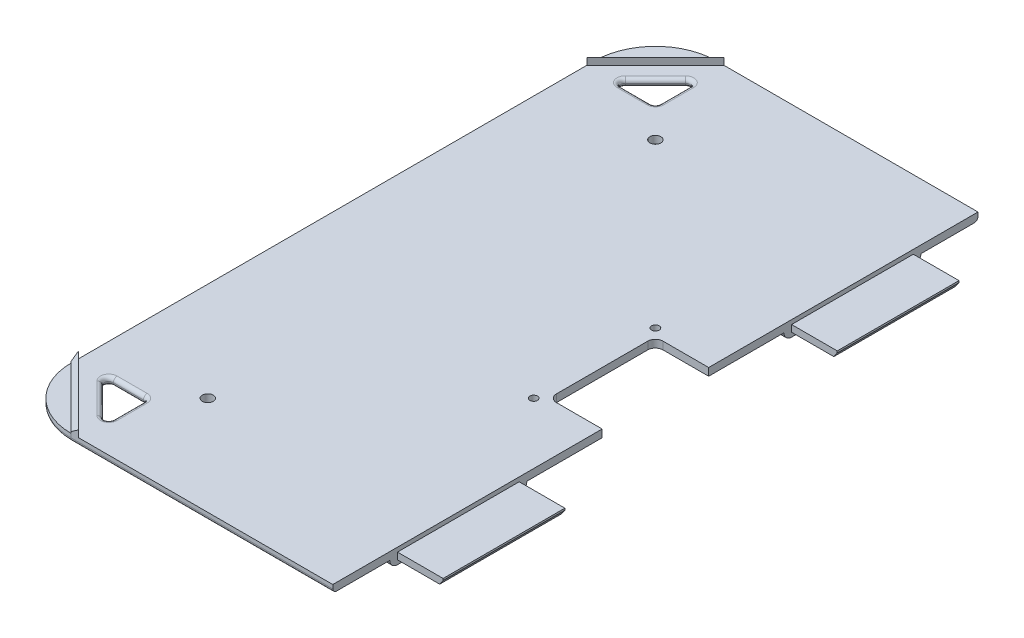
SolidWorks part; units mm, degrees
ref_plane "Front Plane" through (0, 0, 0) normal (0, 0, 1) x (1, 0, 0)
ref_plane "Top Plane" through (0, 0, 0) normal (0, 1, 0) x (1, 0, 0)
ref_plane "Right Plane" through (0, 0, 0) normal (1, 0, 0) x (0, 0, -1)
sketch "Sketch1" plane through (0, 0, 0) normal (0, 1, 0) x (1, 0, 0)
  line L0 (0, -134.62) -> (0, 134.62)
  line L1 (-134.62, -134.62) -> (134.62, -134.62)
  line L2 (-134.62, -134.62) -> (-134.62, 134.62)
  line L3 (-134.62, 134.62) -> (134.62, 134.62)
  line L4 (134.62, -134.62) -> (134.62, 134.62)
  line L5 (-134.62, -134.62) -> (134.62, 134.62) construction
  line L6 (-134.62, 134.62) -> (134.62, -134.62) construction
  point P0 (0, 0)
  point P9 (0, 0)
  dimension "D1" = 269.24
extrude "Boss-Extrude1" add sketch "Sketch1" along normal blind 3.175 contours L3 L2 L1 L0 region at (-67.31, 0, 0)
sketch "Sketch2" plane through (0, 3.175, 0) normal (0, 1, 0) x (1, 0, 0)
  line L0 (-109.22, -134.62) -> (-134.62, -109.22)
  line L1 (-109.22, -134.62) -> (-106.045, -134.62)
  line L2 (-106.045, -134.62) -> (-134.62, -106.045)
  line L3 (-134.62, -106.045) -> (-134.62, -109.22)
  line L4 (0, 134.62) -> (-134.62, 134.62)
  line L5 (-134.62, 134.62) -> (-134.62, -134.62)
  line L6 (-134.62, -134.62) -> (0, -134.62)
  line L7 (0, -134.62) -> (0, 134.62)
  line L8 (0, 134.62) -> (-134.62, 134.62)
  line L9 (-134.62, 134.62) -> (-134.62, -134.62)
  line L10 (-134.62, -134.62) -> (0, -134.62)
  line L11 (0, -134.62) -> (0, 134.62)
  line L12 (-109.22, 134.62) -> (-134.62, 109.22)
  line L13 (-134.62, 109.22) -> (-134.62, 106.045)
  line L14 (-134.62, 106.045) -> (-106.045, 134.62)
  line L15 (-106.045, 134.62) -> (-109.22, 134.62)
  line L16 (-120.3325, 120.3325) -> (-115.3934, 115.3934)
  line L17 (-120.3325, -120.3325) -> (-115.3934, -115.3934)
  line L18 (-124.9184, -105.8684) -> (-105.8684, -124.9184)
  line L19 (-105.8684, -124.9184) -> (-105.8684, -105.8684)
  line L20 (-105.8684, -105.8684) -> (-124.9184, -105.8684)
  line L21 (-124.9184, 105.8684) -> (-105.8684, 124.9184)
  line L22 (-105.8684, 124.9184) -> (-105.8684, 105.8684)
  line L23 (-105.8684, 105.8684) -> (-124.9184, 105.8684)
  line L24 (-120.3325, 120.3325) -> (-93.3917, 93.3917)
  line L25 (-120.3325, -120.3325) -> (-93.3917, -93.3917)
  circle A0 centre (-93.3917, 93.3917) radius 2.286
  circle A1 centre (-93.3917, -93.3917) radius 2.286
  point P12 (-120.3325, -120.3325)
  point P14 (-120.3325, 120.3325)
  point P21 (-115.3934, -115.3934)
  point P25 (-115.3934, 115.3934)
  line M24 (-134.62, 134.62) -> (-134.62, -134.62)
  line M25 (-134.62, -134.62) -> (0, -134.62)
  dimension "D17" = 4.572
  dimension "D2" = 25.4
  dimension "D3" = 25.4
  dimension "D4" = 3.175
  dimension "D5" = 25.4
  dimension "D6" = 3.175
  dimension "D7" = 25.4
  dimension "D8" = 3.175
  dimension "D9" = 6.985
  dimension "D10" = 6.985
  dimension "D11" = 90
  dimension "D12" = 90
  dimension "D13" = 19.05
  dimension "D14" = 90
  dimension "D15" = 19.05
  dimension "D16" = 38.1
  dimension "D18" = 90
  dimension "D19" = 90
  dimension "D1" = 0
extrude "Boss-Extrude2" add sketch "Sketch2" along normal blind 3.175 contours L9 L14 L8 L12 | L2 L0 M25 M24 region at (-121.1107, 3.175, 121.1107) region at (-121.1107, 3.175, -121.1107)
extrude "Cut-Extrude1" cut sketch "Sketch2<3>" against normal up to next contours L23 L21 L22 | L19 L20 L18 | A1 | A0
sketch "Sketch2<3>" plane through (0, 3.175, 0) normal (0, 1, 0) x (1, 0, 0) same geometry as "Sketch2"
chamfer "Chamfer1" distance 2.54 2 edges at (-121.92, 6.35, -121.92) (-121.92, 6.35, 121.92)
fillet "Fillet1" radius 1.905 6 edges at (-105.8684, 1.5875, -105.8684) (-124.9184, 1.5875, -105.8684) (-105.8684, 1.5875, -124.9184) (-105.8684, 1.5875, 124.9184) (-105.8684, 1.5875, 105.8684) (-124.9184, 1.5875, 105.8684)
fillet "Fillet2" radius 1.5875 24 edges at (-107.0443, 0, 122.0793) (-105.8684, 0, 114.0463) (-106.4263, 0, 106.4263) (-114.0463, 0, 105.8684) (-122.0793, 0, 107.0443) (-122.0793, 3.175, 107.0443) (-114.0463, 3.175, 105.8684) (-106.4263, 3.175, 106.4263) (-105.8684, 3.175, 114.0463) (-107.0443, 3.175, 122.0793) (-122.0793, 3.175, -107.0443) (-114.0463, 3.175, -105.8684) (-106.4263, 3.175, -106.4263) (-105.8684, 3.175, -114.0463) (-107.0443, 3.175, -122.0793) (-107.0443, 0, -122.0793) (-105.8684, 0, -114.0463) (-106.4263, 0, -106.4263) (-114.0463, 0, -105.8684) (-122.0793, 0, -107.0443) (-115.3934, 0, 115.3934) (-115.3934, 3.175, 115.3934) (-115.3934, 3.175, -115.3934) (-115.3934, 0, -115.3934)
fillet "Fillet3" radius 25.4 2 edges at (-134.62, 1.5875, 134.62) (-134.62, 1.5875, -134.62)
fillet "Fillet4" radius 1.5875 5 edges at (-127.1805, 0, -127.1805) (-54.61, 0, -134.62) (-134.62, 0, 0) (-127.1805, 0, 127.1805) (-54.61, 0, 134.62)
sketch "Sketch3" plane through (0, 0, 0) normal (0, -1, 0) x (1, 0, 0)
  line L1 (0, 28.575) -> (-31.75, 28.575)
  line L2 (0, 28.575) -> (0, -28.575)
  line L3 (0, -28.575) -> (-31.75, -28.575)
  line L4 (-109.22, -133.0325) -> (0, -133.0325)
  line L5 (0, -133.0325) -> (0, 133.0325)
  line L6 (0, 133.0325) -> (-109.22, 133.0325)
  line L7 (-133.0325, 109.22) -> (-133.0325, -109.22)
  line L8 (-109.22, -133.0325) -> (0, -133.0325)
  line L9 (0, -133.0325) -> (0, 133.0325)
  line L10 (0, 133.0325) -> (-109.22, 133.0325)
  line L11 (-133.0325, 109.22) -> (-133.0325, -109.22)
  line L12 (-31.75, 28.575) -> (-31.75, -28.575)
  line L13 (-31.75, 110.8075) -> (0, 110.8075)
  line L14 (-31.75, 110.8075) -> (-31.75, 53.6575)
  line L15 (-31.75, 53.6575) -> (0, 53.6575)
  line L16 (0, 110.8075) -> (0, 53.6575)
  line L17 (-31.75, -53.6575) -> (0, -53.6575)
  line L18 (-31.75, -53.6575) -> (-31.75, -110.8075)
  line L19 (-31.75, -110.8075) -> (0, -110.8075)
  line L20 (0, -53.6575) -> (0, -110.8075)
  arc A2 (-133.0325, -109.22) -> (-109.22, -133.0325) centre (-109.22, -109.22) ccw
  arc A3 (-109.22, 133.0325) -> (-133.0325, 109.22) centre (-109.22, 109.22) ccw
  arc A4 (-133.0325, -109.22) -> (-109.22, -133.0325) centre (-109.22, -109.22) ccw
  arc A5 (-109.22, 133.0325) -> (-133.0325, 109.22) centre (-109.22, 109.22) ccw
  point P12 (0, 0)
  point P22 (-31.75, -82.2325)
  point P23 (-31.75, 82.2325)
  dimension "D2" = 57.15
  dimension "D3" = 31.75
  dimension "D4" = 50.8
  dimension "D5" = 50.8
  dimension "D1" = 0
extrude "Boss-Extrude3" add sketch "Sketch3" along normal blind 3.175 contours L14 L15 L9 L13 | L18 L19 L9 L17 region at (-15.875, 0, 82.2325) region at (-15.875, 0, -82.2325)
sketch "Sketch4" plane through (0, 0, 0) normal (1, 0, 0) x (0, 0, -1)
  line L0 (-110.8075, 0) -> (-110.8075, 3.175)
  line L1 (-53.6575, 0) -> (-53.6575, 3.175)
  line L2 (53.6575, 0) -> (53.6575, 3.175)
  line L3 (28.575, 0) -> (28.575, 3.175)
  line L4 (53.6575, 0) -> (53.6575, 3.175)
  line L5 (110.8075, 0) -> (110.8075, 3.175)
  line L6 (28.575, 3.175) -> (53.6575, 3.175)
  line L7 (-53.6575, 3.175) -> (-110.8075, 3.175)
  line L9 (107.6325, -1.397) -> (56.8325, -1.397)
  line L10 (107.6325, -1.397) -> (107.6325, 1.397)
  line L11 (107.6325, 1.397) -> (56.8325, 1.397)
  line L12 (56.8325, -1.397) -> (56.8325, 1.397)
  line L13 (107.6325, -1.397) -> (56.8325, 1.397) construction
  line L14 (107.6325, 1.397) -> (56.8325, -1.397) construction
  line L15 (25.4, -1.397) -> (-25.4, -1.397)
  line L16 (-133.0325, 0) -> (-110.8075, 0)
  line L17 (-110.8075, 0) -> (-110.8075, -3.175)
  line L18 (-110.8075, -3.175) -> (-53.6575, -3.175)
  line L19 (-53.6575, -3.175) -> (-53.6575, 0)
  line L20 (-53.6575, 0) -> (53.6575, 0)
  line L25 (53.6575, 0) -> (53.6575, -3.175)
  line L26 (53.6575, -3.175) -> (110.8075, -3.175)
  line L27 (110.8075, -3.175) -> (110.8075, 0)
  line L28 (110.8075, 0) -> (133.0325, 0)
  line L29 (134.62, 1.5875) -> (134.62, 3.175)
  line L30 (134.62, 3.175) -> (-134.62, 3.175)
  line L31 (-134.62, 3.175) -> (-134.62, 1.5875)
  line L33 (-110.8075, 0) -> (-110.8075, -3.175)
  line L34 (-110.8075, -3.175) -> (-53.6575, -3.175)
  line L35 (-53.6575, -3.175) -> (-53.6575, 0)
  line L41 (53.6575, 0) -> (53.6575, -3.175)
  line L42 (53.6575, -3.175) -> (110.8075, -3.175)
  line L43 (110.8075, -3.175) -> (110.8075, 0)
  line L46 (110.8075, 3.175) -> (53.6575, 3.175)
  line L48 (25.4, -1.397) -> (25.4, 1.397)
  line L49 (25.4, 1.397) -> (-25.4, 1.397)
  line L50 (-25.4, -1.397) -> (-25.4, 1.397)
  line L51 (25.4, -1.397) -> (-25.4, 1.397) construction
  line L52 (25.4, 1.397) -> (-25.4, -1.397) construction
  line L53 (-56.8325, -1.397) -> (-107.6325, -1.397)
  line L54 (-56.8325, -1.397) -> (-56.8325, 1.397)
  line L55 (-56.8325, 1.397) -> (-107.6325, 1.397)
  line L56 (-107.6325, -1.397) -> (-107.6325, 1.397)
  line L57 (-56.8325, -1.397) -> (-107.6325, 1.397) construction
  line L58 (-56.8325, 1.397) -> (-107.6325, -1.397) construction
  arc A2 (133.0325, 0) -> (134.62, 1.5875) centre (133.0325, 1.5875) ccw
  arc A3 (-134.62, 1.5875) -> (-133.0325, 0) centre (-133.0325, 1.5875) ccw
  point P10 (-82.2325, -3.175)
  point P20 (0, -3.175)
  point P22 (82.2325, -3.175)
  point P24 (82.2325, 0)
  point P33 (0, 0)
  point P40 (-82.2325, 0)
  dimension "D2" = 2.794
  dimension "D3" = 50.8
  dimension "D1" = 0
extrude "Boss-Extrude4" add sketch "Sketch4" along normal blind 19.05 contours L56 L53 L54 L55 | L12 L9 L10 L11 region at (0, 0, -82.2325) region at (0, 0, 82.2325)
fillet "Fillet5" radius 12.7 4 edges at (-31.75, -1.5875, 53.6575) (-31.75, -1.5875, 110.8075) (-31.75, -1.5875, -53.6575) (-31.75, -1.5875, -110.8075)
fillet "Fillet6" radius 3.175 10 edges at (-9.525, -3.175, -53.6575) (-28.0303, -3.175, -57.3772) (-31.75, -3.175, -82.2325) (-28.0303, -3.175, -107.0878) (-9.525, -3.175, 110.8075) (-28.0303, -3.175, 107.0878) (-31.75, -3.175, 82.2325) (-28.0303, -3.175, 57.3772) (-9.525, -3.175, -110.8075) (-9.525, -3.175, 53.6575)
sketch "Sketch5" plane through (0, 0, 0) normal (0, -1, 0) x (1, 0, 0)
  line L1 (-22.225, -22.225) -> (22.225, -22.225)
  line L2 (-22.225, -22.225) -> (-22.225, 22.225)
  line L3 (-22.225, 22.225) -> (22.225, 22.225)
  line L4 (22.225, -22.225) -> (22.225, 22.225)
  line L5 (-22.225, -22.225) -> (22.225, 22.225) construction
  line L6 (-22.225, 22.225) -> (22.225, -22.225) construction
  line L7 (-25.4, -25.4) -> (25.4, -25.4)
  line L8 (-25.4, -25.4) -> (-25.4, 25.4)
  line L9 (-25.4, 25.4) -> (25.4, 25.4)
  line L10 (25.4, -25.4) -> (25.4, 25.4)
  line L11 (-25.4, -25.4) -> (25.4, 25.4) construction
  line L12 (0, -110.8075) -> (-19.05, -110.8075)
  line L13 (-31.75, -98.1075) -> (-31.75, -66.3575)
  line L14 (-19.05, -53.6575) -> (0, -53.6575)
  line L15 (0, -53.6575) -> (0, 53.6575)
  line L16 (0, 53.6575) -> (-19.05, 53.6575)
  line L17 (-31.75, 66.3575) -> (-31.75, 98.1075)
  line L18 (-19.05, 110.8075) -> (0, 110.8075)
  line L19 (0, 110.8075) -> (0, 133.0325)
  line L20 (0, 133.0325) -> (-109.22, 133.0325)
  line L21 (-133.0325, 109.22) -> (-133.0325, -109.22)
  line L22 (-109.22, -133.0325) -> (0, -133.0325)
  line L23 (0, -133.0325) -> (0, -110.8075)
  line L24 (0, -110.8075) -> (-19.05, -110.8075)
  line L25 (-31.75, -98.1075) -> (-31.75, -66.3575)
  line L26 (-19.05, -53.6575) -> (0, -53.6575)
  line L27 (0, -53.6575) -> (0, 53.6575)
  line L28 (0, 53.6575) -> (-19.05, 53.6575)
  line L29 (-31.75, 66.3575) -> (-31.75, 98.1075)
  line L30 (-19.05, 110.8075) -> (0, 110.8075)
  line L31 (0, 110.8075) -> (0, 133.0325)
  line L32 (0, 133.0325) -> (-109.22, 133.0325)
  line L33 (-133.0325, 109.22) -> (-133.0325, -109.22)
  line L34 (-109.22, -133.0325) -> (0, -133.0325)
  line L35 (0, -133.0325) -> (0, -110.8075)
  line L36 (-25.4, 25.4) -> (25.4, -25.4) construction
  circle A0 centre (-25.4, 25.4) radius 1.5875
  circle A1 centre (-25.4, -25.4) radius 1.5875
  arc A6 (-31.75, -98.1075) -> (-19.05, -110.8075) centre (-19.05, -98.1075) ccw
  arc A7 (-19.05, -53.6575) -> (-31.75, -66.3575) centre (-19.05, -66.3575) ccw
  arc A8 (-31.75, 66.3575) -> (-19.05, 53.6575) centre (-19.05, 66.3575) ccw
  arc A9 (-19.05, 110.8075) -> (-31.75, 98.1075) centre (-19.05, 98.1075) ccw
  arc A10 (-109.22, 133.0325) -> (-133.0325, 109.22) centre (-109.22, 109.22) ccw
  arc A11 (-133.0325, -109.22) -> (-109.22, -133.0325) centre (-109.22, -109.22) ccw
  arc A12 (-31.75, -98.1075) -> (-19.05, -110.8075) centre (-19.05, -98.1075) ccw
  arc A13 (-19.05, -53.6575) -> (-31.75, -66.3575) centre (-19.05, -66.3575) ccw
  arc A14 (-31.75, 66.3575) -> (-19.05, 53.6575) centre (-19.05, 66.3575) ccw
  arc A15 (-19.05, 110.8075) -> (-31.75, 98.1075) centre (-19.05, 98.1075) ccw
  arc A16 (-109.22, 133.0325) -> (-133.0325, 109.22) centre (-109.22, 109.22) ccw
  arc A17 (-133.0325, -109.22) -> (-109.22, -133.0325) centre (-109.22, -109.22) ccw
  point P2 (0, 0)
  point P21 (0, 0)
  line M47 (0, -53.6575) -> (0, 53.6575)
  dimension "D4" = 3.175
  dimension "D2" = 44.45
  dimension "D3" = 50.8
  dimension "D1" = 0
extrude "Cut-Extrude2" cut sketch "Sketch5" against normal up to next contours L3 L2 L1 M47 | A0 | A1 region at (-11.1125, 0, 0)
fillet "Fillet7" radius 3.175 2 edges at (-22.225, 1.5875, -22.225) (-22.225, 1.5875, 22.225)
chamfer "Chamfer2" distance 2.032 angle 35 2 edges at (19.05, -1.397, -82.2325) (19.05, -1.397, 82.2325) first distance on face at (19.05, 0, -82.2325) first distance on face at (19.05, 0, 82.2325)
